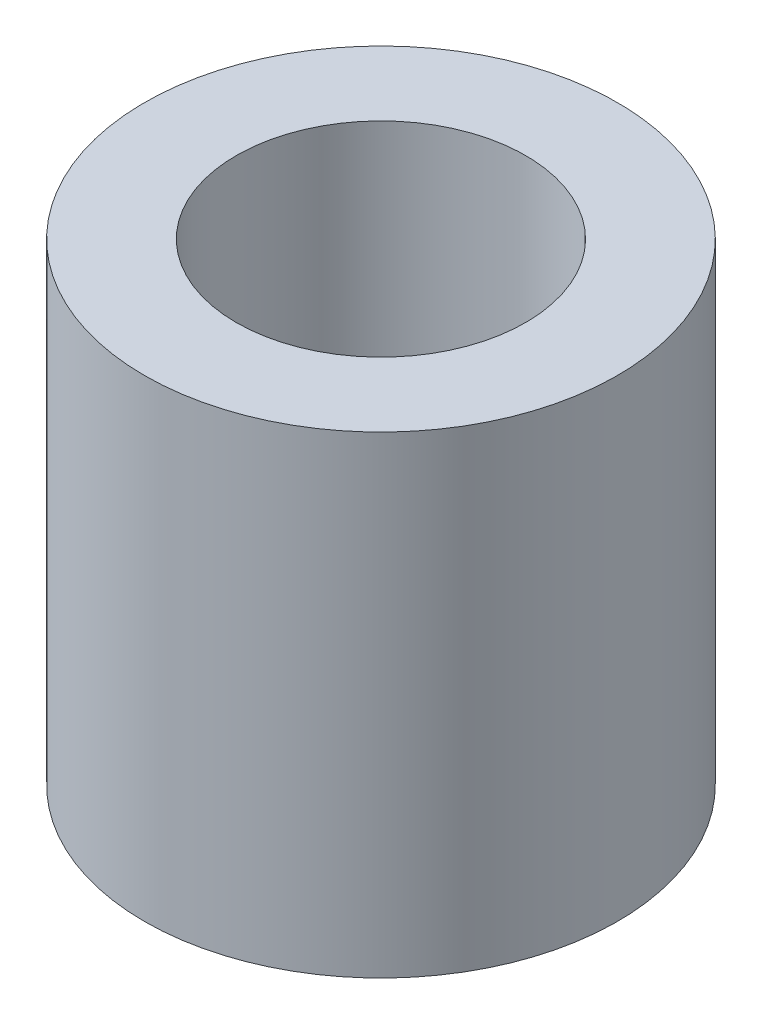
SolidWorks part; units mm, degrees
ref_plane "Alzado" through (0, 0, 0) normal (0, 0, 1) x (1, 0, 0)
ref_plane "Planta" through (0, 0, 0) normal (0, 1, 0) x (1, 0, 0)
ref_plane "Vista lateral" through (0, 0, 0) normal (1, 0, 0) x (0, 0, -1)
sketch "Croquis1" plane through (0, 0, 0) normal (0, 1, 0) x (1, 0, 0)
  circle A0 centre (0, 0) radius 2.5
  circle A1 centre (0, 0) radius 1.53
  dimension "D1" = 3.06
  dimension "D2" = 5
extrude "Saliente-Extruir1" add sketch "Croquis1" along normal blind 5
